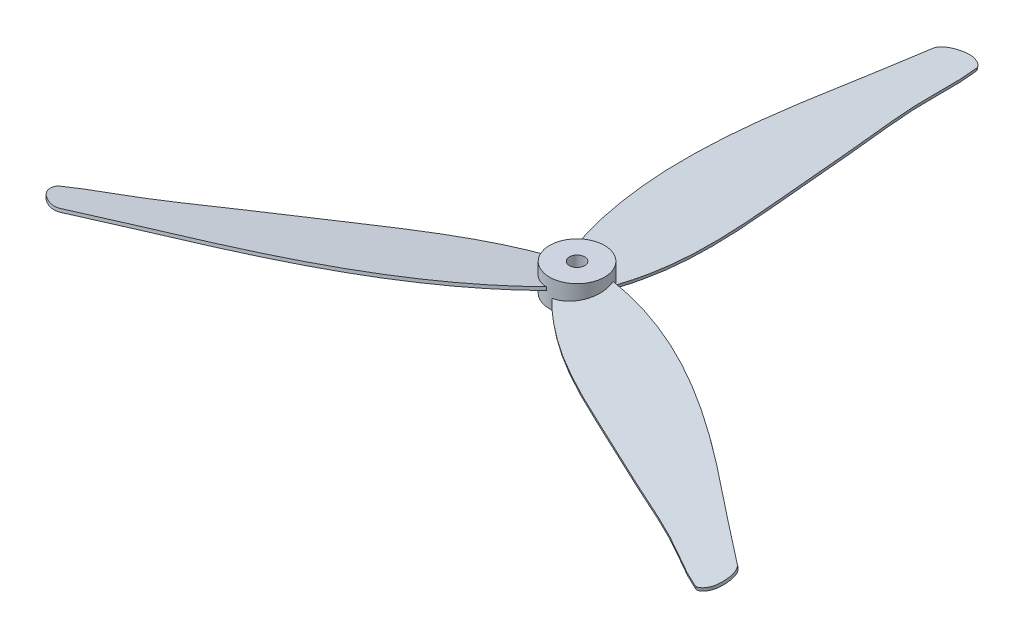
SolidWorks part; units mm, degrees
material "A-Glass Fiber"
ref_plane "Front Plane" through (0, 0, 0) normal (0, 0, 1) x (1, 0, 0)
ref_plane "Top Plane" through (0, 0, 0) normal (0, 1, 0) x (1, 0, 0)
ref_plane "Right Plane" through (0, 0, 0) normal (1, 0, 0) x (0, 0, -1)
sketch "Sketch1" plane through (0, 0, 0) normal (0, 1, 0) x (1, 0, 0)
  circle A0 centre (0, 0) radius 9
  circle A1 centre (0, 0) radius 2.5
  dimension "D1" = 18
  dimension "D2" = 5
extrude "Boss-Extrude1" add sketch "Sketch1" along normal blind 9
sketch "Sketch3" plane through (0, 0, 0) normal (0, 1, 0) x (1, 0, 0)
  line L0 (0, 0) -> (0, 32.3409) construction
  line L1 (0, 0) -> (86.3188, -49.8362) construction
  dimension "D1" = 120
ref_plane "Plane1" through (0, 0, 0) normal (-0.0782, 0.9877, 0.1355) x (0.866, 0, 0.5)
sketch "Sketch2" plane through (0, 0, 0) normal (0.0782, -0.9877, -0.1355) x (0.5031, -0.0782, 0.8607)
  line L0 (-0.0729, 0) -> (109.2834, -64.577) construction
  arc A3 (7.0572, 3.5223) -> (-0.8103, -7.8456) centre (0, 0) cw
  spline S0 degree 3 poles (-0.8103, -7.8456) (14.8456, -26.5282) (50.11, -46.9687) (87.5823, -60.2779) (104.3944, -67.4966) (108.6947, -65.6224) (111.8395, -62.2937) (111.6744, -59.1449) (110.3348, -58.1895) (105.388, -54.6473) (93.4703, -48.5314) (77.381, -36.6533) (48.7521, -17.4899) (26.9641, -1.2792) (7.0572, 3.5223) knots 0 0 0 0 0.282933 0.466483 0.471857 0.495006 0.514383 0.523355 0.526651 0.533187 0.595375 0.682473 0.767936 1 1 1 1
  point P6 (0, 0)
  point P8 (-0.7644, -7.4017)
  point P10 (7.0572, 3.5223)
  dimension "D1" = 127
extrude "Boss-Extrude2" add sketch "Sketch2" along normal blind 1 from offset 4.5 offset against normal yes
pattern_circular "CirPattern1" count 3 over 360 about axis through (0, 9, 0) along (0, 1, 0) of "Boss-Extrude2"
